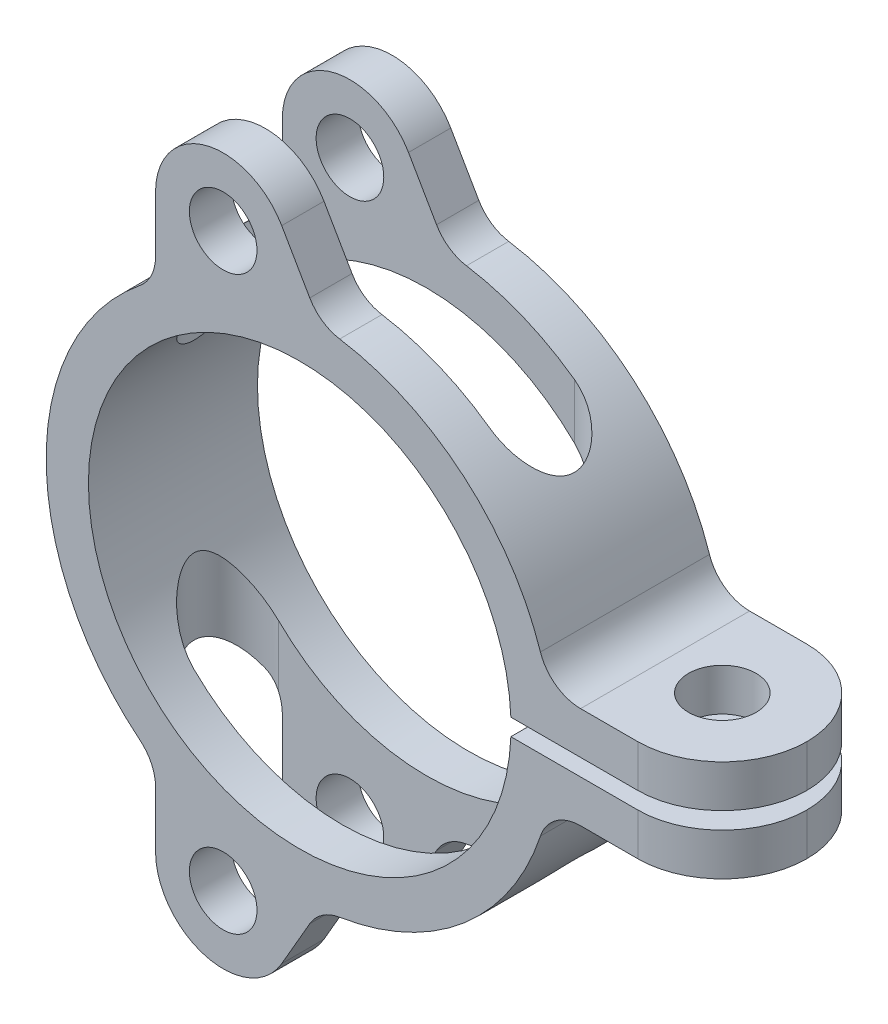
SolidWorks part; units mm, degrees
ref_plane "Front Plane" through (0, 0, 0) normal (1, 0, 0) x (0, 1, 0)
ref_plane "Top Plane" through (0, 0, 0) normal (0, 0, 1) x (0, 1, 0)
ref_plane "Right Plane" through (0, 0, 0) normal (0, 1, 0) x (-1, 0, 0)
sketch "Sketch1" plane through (0, 0, 0) normal (0, 0, 1) x (0, 1, 0)
  line L0 (0, 0) -> (0, -50) construction
  line L1 (-1, 0) -> (-1, -50)
  line L2 (1, 0) -> (1, -50)
  line L3 (-6, 0) -> (-6, -50)
  line L4 (6, 0) -> (6, -50)
  line L5 (0, 0) -> (-33.8074, 9.0587) construction
  line L6 (0, 0) -> (0, 46.0151) construction
  line L7 (-33.8074, 9.0587) -> (-63.6638, 17.0587) construction
  line L8 (-63.6638, 17.0587) -> (-24.678, 17.0587)
  line L9 (-63.6638, 17.0587) -> (-29.9011, -2.4343)
  line L10 (63.6638, 17.0587) -> (29.9011, -2.4343)
  line L11 (63.6638, 17.0587) -> (24.678, 17.0587)
  line L12 (-6, -50) -> (6, -50)
  line L13 (-6, 0) -> (6, 0)
  line L14 (24.678, 17.0587) -> (-24.678, 17.0587)
  line L15 (-29.9011, -2.4343) -> (29.9011, -2.4343)
  circle A0 centre (0, 0) radius 25
  circle A1 centre (0, 0) radius 30
  circle A2 centre (-33.8074, 9.0587) radius 4
  circle A3 centre (-33.8074, 9.0587) radius 8
  circle A4 centre (33.8074, 9.0587) radius 4
  circle A5 centre (33.8074, 9.0587) radius 8
  dimension "D1" = 60
  dimension "D2" = 50
  dimension "D10" = 8
  dimension "D11" = 16
  dimension "D3" = 50
  dimension "D8" = 35
  dimension "D9" = 75
  dimension "D12" = 330
  dimension "D4" = 1
  dimension "D5" = 1
  dimension "D6" = 5
  dimension "D7" = 5
extrude "Boss-Extrude1" add sketch "Sketch1" along normal blind 20 contours L4 A1 L15 A0 | A1 A5 L14 A0 L15 | L14 A1 A0 | A3 A1 L15 A0 L14 | L15 A1 L3 A0 | L3 A1 L1 A0 | L2 A1 L4 A0 | A1 L3 L12 L1 | A1 L2 L12 L4 | A5 A1 | A5 A1 A4 | A1 A3 A2 | A1 A3 | A3 A1 L8 | A3 L9 A1 | L10 A5 A1 | A1 A5 L11 region at (27.2339, -3.51, 0) region at (39.8791, -3.5121, 0) region at (17.0083, -19.3939, 0) region at (27.2339, 3.51, 0) region at (-7.7679, -25.1142, 0) region at (39.8791, 3.5121, 0) region at (17.0083, 19.3939, 0) region at (-0.0966, -31.9873, 0) region at (-17.5689, -21.4768, 0) region at (-7.7679, 25.1142, 0) region at (-11.0727, -41.3239, 0) region at (-7.4207, -27.6943, 0) region at (-15.91, -27.7501, 0) region at (-0.0966, 31.9873, 0) region at (-15.91, 27.7501, 0) region at (-1.2773, 33.8754, 0) region at (-7.4207, 27.6943, 0)
fillet "Fillet1" radius 10 4 edges at (50, 3.5, 0) (50, -3.5, 0) (50, -3.5, 20) (50, 3.5, 20)
sketch "Sketch2" plane through (0, 0, 0) normal (0, 1, 0) x (-1, 0, 0)
  line L0 (-40, 10) -> (-17.5, 10) construction
  line L1 (-17.5, 15) -> (17.5, 15)
  line L2 (17.5, 15) -> (17.5, 5)
  line L3 (17.5, 5) -> (-17.5, 5)
  circle A0 centre (-40, 10) radius 4
  circle A1 centre (-17.5, 10) radius 5
  circle A2 centre (17.5, 10) radius 5
  dimension "D1" = 8
  dimension "D3" = 10
  dimension "D4" = 35
  dimension "D2" = 22.5
extrude "Cut-Extrude1" cut sketch "Sketch2" against normal through all both and the other way through all contours A1 | A2 L1 A1 L3 | L2 A2 | L2 A2 | A0 region at (0, 0, 10) region at (17.5, 0, 10) region at (-19.6221, 0, 10) region at (-15.3779, 0, 10)
fillet "Fillet2" radius 5 10 edges at (29.3939, -6, 10) (2.4343, -29.9011, 17.5) (2.4343, -29.9011, 2.5) (-17.0587, -24.678, 17.5) (-17.0587, -24.678, 2.5) (-17.0587, 24.678, 17.5) (-17.0587, 24.678, 2.5) (2.4343, 29.9011, 2.5) (2.4343, 29.9011, 17.5) (29.3939, 6, 10)
